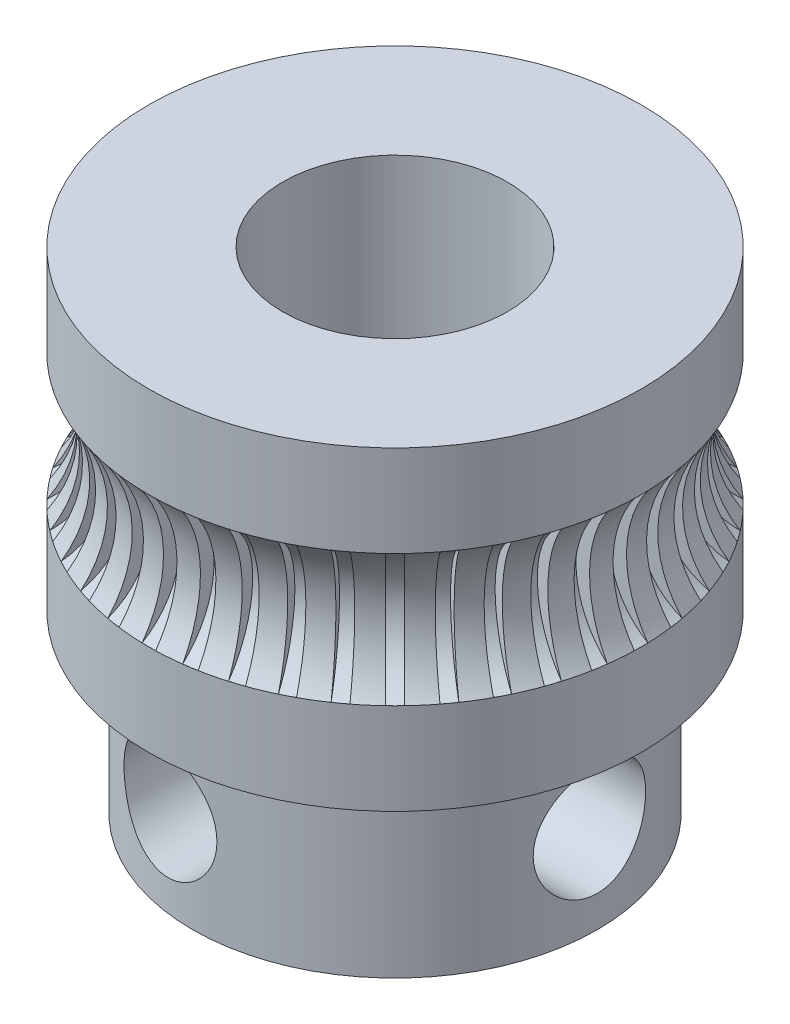
SolidWorks part; units mm, degrees
material "Latón"
ref_plane "Alzado" through (0, 0, 0) normal (0, 0, 1) x (1, 0, 0)
ref_plane "Planta" through (0, 0, 0) normal (0, 1, 0) x (1, 0, 0)
ref_plane "Vista lateral" through (0, 0, 0) normal (1, 0, 0) x (0, 0, -1)
ref_plane "Plano1" through (0, 0, -56.4) normal (0, 0, 1) x (1, 0, 0)
sketch "Croquis1" plane through (0, 0, -56.4) normal (0, 0, 1) x (1, 0, 0)
  line L0 (80.975, 56.4264) -> (75.5, 56.4264)
  line L1 (75.5, 56.4264) -> (75.5, 49.4264)
  line L2 (75.5, 49.4264) -> (80.975, 49.4264)
  line L3 (80.975, 49.4264) -> (80.975, 56.4264)
  line L4 (75.5, 56.4264) -> (75.5, 49.4264) construction
revolve "Revolución1" add sketch "Croquis1" angle 360 about L4 reverse direction yes
sketch "Croquis2" plane through (0, 49.4264, 0) normal (0, -1, 0) x (1, 0, 0)
  circle A0 centre (75.5, -56.4) radius 4.5
extrude "Saliente-Extruir1" add sketch "Croquis2" along normal blind 3.9
hole_wizard "Diámetro de taladro Ø5.0 (5)1" positions "Croquis4" profile "Croquis3" hole size "Ø5.0" standard "Ansi Metric"
sketch "Croquis4" plane through (0, 56.4264, 0) normal (0, 1, 0) x (1, 0, 0)
  point P0 (75.5, 56.4)
sketch "Croquis3" plane through (75.5, 56.4264, -56.4) normal (1, 0, 0) x (0, 0, 1)
  line L0 (0, 0) -> (0, 10.9)
  line L1 (0, 10.9) -> (2.5, 10.9)
  line L2 (2.5, 10.9) -> (2.5, 0)
  line L5 (2.5, 0) -> (0, 0)
  line L11 (0, -6.35) -> (0, 107.95) construction
  dimension "Diámetro de taladro hasta el siguiente" = 5
  dimension "Profundidad de taladro hasta el siguiente" = 10.9
ref_plane "Plano2" through (77.6651, 0, 0) normal (-1, 0, 0) x (0, 0, 1)
hole_wizard "Diámetro de taladro Ø2.5 (2.5)1" positions "Croquis6" profile "Croquis5" hole size "Ø2.5" standard "Ansi Metric"
sketch "Croquis6" plane through (77.6651, 0, 0) normal (-1, 0, 0) x (0, 0, 1)
  point P0 (-56.4, 47.4764)
sketch "Croquis5" plane through (77.6651, 47.4764, -56.4) normal (0, 1, 0) x (0, 0, 1)
  line L0 (0, 0) -> (0, 3.3099)
  line L1 (0, 3.3099) -> (1.25, 3.3099)
  line L2 (1.25, 3.3099) -> (1.25, 0)
  line L5 (1.25, 0) -> (0, 0)
  line L11 (0, -6.35) -> (0, 107.95) construction
  dimension "Diámetro de taladro hasta el siguiente" = 2.5
  dimension "Profundidad de taladro hasta el siguiente" = 3.3099
ref_plane "Plano3" through (0, 0, -54.8854) normal (0, 0, -1) x (-1, 0, 0)
hole_wizard "Diámetro de taladro Ø2.5 (2.5)2" positions "Croquis8" profile "Croquis7" hole size "Ø2.5" standard "Ansi Metric"
sketch "Croquis8" plane through (0, 0, -54.8854) normal (0, 0, -1) x (-1, 0, 0)
  point P0 (-74.761, 47.4594)
sketch "Croquis7" plane through (74.761, 47.4594, -54.8854) normal (1, 0, 0) x (0, 1, 0)
  line L0 (0, 0) -> (0, 3.9604)
  line L1 (0, 3.9604) -> (1.25, 3.9604)
  line L2 (1.25, 3.9604) -> (1.25, 0)
  line L5 (1.25, 0) -> (0, 0)
  line L11 (0, -6.35) -> (0, 107.95) construction
  dimension "Diámetro de taladro hasta el siguiente" = 2.5
  dimension "Profundidad de taladro hasta el siguiente" = 3.9604
ref_plane "Plano4" through (75.5, 0, 0) normal (-1, 0, 0) x (0, 0, 1)
sketch "Croquis15" plane through (75.5, 0, 0) normal (-1, 0, 0) x (0, 0, 1)
  circle A0 centre (-48.9, 52.9264) radius 2.5
sketch "Croquis23" plane through (75.5, 0, 0) normal (-1, 0, 0) x (0, 0, 1)
  circle A0 centre (-50.0644, 52.9264) radius 1.7
extrude "Cortar-Extruir1" cut sketch "Croquis23" against normal mid plane 0.3
sketch3d "Croquis3D1"
  point P0 (75.5, 56.4264, -56.4)
  point P1 (75.5, 54.3925, -56.4)
ref_axis "Eje1" through (75.5, 56.4264, -56.4) along (0, -1, 0)
pattern_circular "MatrizC1" count 40 over 360 about axis through (75.5, 56.4264, -56.4) along (0, -1, 0) of "Cortar-Extruir1"
sketch "Croquis24" plane through (0, 56.4264, 0) normal (0, 1, 0) x (1, 0, 0)
  circle A0 centre (75.5, 56.4) radius 7.5
  dimension "D1" = 15
sweep "Cortar-Barrer1" cut profiles "Croquis15" path "Croquis24"
